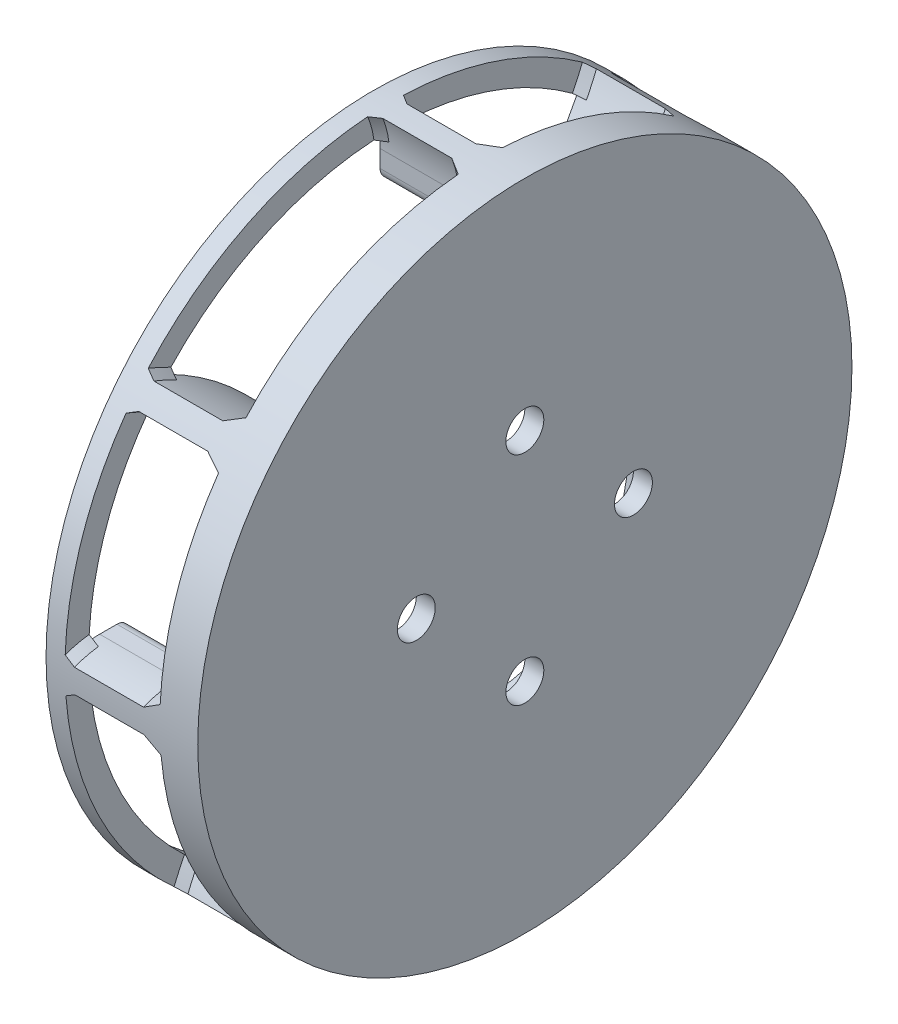
SolidWorks part; units mm, degrees
ref_plane "Front Plane" through (0, 0, 0) normal (0, 0, 1) x (1, 0, 0)
ref_plane "Top Plane" through (0, 0, 0) normal (0, 1, 0) x (1, 0, 0)
ref_plane "Right Plane" through (0, 0, 0) normal (1, 0, 0) x (0, 0, -1)
sketch "Sketch1" plane through (0, 0, 0) normal (1, 0, 0) x (0, 0, -1)
  circle A0 centre (0, 0) radius 34.5
  circle A1 centre (0, 11.45) radius 2
  circle A2 centre (11.45, 0) radius 2
  circle A3 centre (0, -11.45) radius 2
  circle A4 centre (-11.45, 0) radius 2
  dimension "D2" = 69
  dimension "D3" = 4
  dimension "D4" = 18.9
  dimension "D1" = 4
extrude "Boss-Extrude1" add sketch "Sketch1" along normal blind 4
sketch "Sketch2" plane through (0, 0, 0) normal (-1, 0, 0) x (0, 0, 1)
  circle A0 centre (0, 0) radius 14.9
  dimension "D1" = 29.8
extrude "Cut-Extrude1" cut sketch "Sketch2" against normal blind 2
sketch "Sketch3" plane through (0, 0, 0) normal (-1, 0, 0) x (0, 0, 1)
  line L0 (15.5302, 15.5302) -> (13.6825, 13.6825)
  line L1 (15.5302, 15.5302) -> (37.9808, -6.9205) construction
  line L2 (0, -1000) -> (0, 49000) construction
  line L3 (15.4786, 11.8865) -> (17.3262, 13.7341)
  line L4 (-1.27, 30.8466) -> (-1.27, 29.02)
  line L5 (1.27, 29.02) -> (1.27, 30.8466)
  arc A0 (15.5302, 15.5302) -> (26.125, 22.5329) centre (37.9808, -6.9205) cw
  circle A1 centre (0, 0) radius 34.5 construction
  circle A2 centre (0, 0) radius 14.9 construction
  arc A3 (13.6825, 13.6825) -> (15.4786, 11.8865) centre (14.5805, 12.7845) ccw
  arc A4 (27.712, 20.5498) -> (17.3262, 13.7341) centre (39.6023, -8.8898) ccw
  arc A5 (26.125, 22.5329) -> (27.712, 20.5498) centre (0, 0) cw
  arc A6 (-1.27, 29.02) -> (1.27, 29.02) centre (0, 29.02) ccw
  arc A7 (-0.5687, 34.4953) -> (-1.27, 30.8466) centre (8.5725, 30.8466) ccw
  arc A8 (1.9713, 34.4436) -> (1.27, 30.8466) centre (11.1124, 30.7946) ccw
  arc A9 (-0.5687, 34.4953) -> (1.9713, 34.4436) centre (0, 0) cw
  dimension "D1" = 31.75
  dimension "D5" = 1.27
  dimension "D7" = 27.75
  dimension "D8" = 1.27
  dimension "D9" = 9.8425
  dimension "D2" = 4.45
  dimension "D3" = 2.54
  dimension "D4" = 45
  dimension "D6" = 2.54
  dimension "D11" = 2.54
extrude "Boss-Extrude2" add sketch "Sketch3" along normal blind 10
ref_axis "Axis1" through (4, 0, 0) along (-1, 0, 0)
pattern_circular "CirPattern4" count 4 over 360 about axis through (4, 0, 0) along (-1, 0, 0) of "Boss-Extrude2"
chamfer "Chamfer3" distance 1 angle 60 40 edges at (0, -16.4024, 12.8103) (0, -13.6825, 11.8865) (0, -14.6063, 14.6063) (0, -20.4739, 19.5667) (0, -12.8103, -16.4024) (0, -11.8865, -13.6825) (0, -14.6063, -14.6063) (0, -19.5667, -20.4739) (0, 22.1825, -17.6548) (0, -22.1825, 17.6548) (0, -17.6548, -22.1825) (0, 16.4024, -12.8103) (0, 13.6825, -11.8865) (0, 14.6063, -14.6063) (0, 20.4739, -19.5667) (0, 12.8103, 16.4024) (0, 11.8865, 13.6825) (0, 14.6063, 14.6063) (0, 29.9333, 1.27) (0, 27.75, 0) (0, 29.9333, -1.27) (0, 32.7044, -1.0931) (0, 32.6781, 1.4518) (0, 1.4518, -32.6781) (0, -1.27, 29.9333) (0, 0, 27.75) (0, 1.27, 29.9333) (0, 1.0931, 32.7044) (0, -29.9333, -1.27) (0, -27.75, 0) (0, -29.9333, 1.27) (0, -32.7044, 1.0931) (0, -32.6781, -1.4518) (0, 1.27, -29.9333) (0, 0, -27.75) (0, -1.27, -29.9333) (0, -1.0931, -32.7044) (0, -1.4518, 32.6781) first distance on face at (0, 0, 14.9)
sketch "Sketch4" plane through (-10, 0, 0) normal (-1, 0, 0) x (0, 0, 1)
  circle A0 centre (0, 0) radius 34.5
  circle A1 centre (0, 0) radius 32
  circle A3 centre (0, 0) radius 34.5 construction
  dimension "D1" = 2.5
extrude "Boss-Extrude3" add sketch "Sketch4" along normal blind 2
chamfer "Chamfer4" distance 1 angle 30 16 edges at (-10, -1.5755, 33.2283) (-10, -24.9216, 22.0195) (-10, -33.2574, 0.9702) (-10, 22.0195, 24.9216) (-10, 0.9702, 33.2574) (-10, 20.0458, 26.5335) (-10, 33.2283, 1.5755) (-10, 26.5335, -20.0458) (-10, 1.5755, -33.2283) (-10, -20.0458, -26.5335) (-10, -33.2283, -1.5755) (-10, -26.5335, 20.0458) (-10, -22.0195, -24.9216) (-10, -0.9702, -33.2574) (-10, 24.9216, -22.0195) (-10, 33.2574, -0.9702) first distance on face at (-6.6928, -1.5115, 32.5214) first distance on face at (-6.6928, -21.2896, 19.6944) first distance on face at (-6.6928, -32.5433, 1.0311) first distance on face at (-7.5196, 19.6944, 21.2896) first distance on face at (-6.6928, 1.0311, 32.5433) first distance on face at (-7.5196, 17.7829, 22.9759) first distance on face at (-6.6928, 32.5214, 1.5115) first distance on face at (-6.6928, 22.9759, -17.7829) first distance on face at (-6.6928, 1.5115, -32.5214) first distance on face at (-6.6928, -17.7829, -22.9759) first distance on face at (-6.6928, -32.5214, -1.5115) first distance on face at (-6.6928, -22.9759, 17.7829) first distance on face at (-6.6928, -19.6944, -21.2896) first distance on face at (-6.6928, -1.0311, -32.5433) first distance on face at (-6.6928, 21.2896, -19.6944) first distance on face at (-6.6928, 32.5433, -1.0311)
